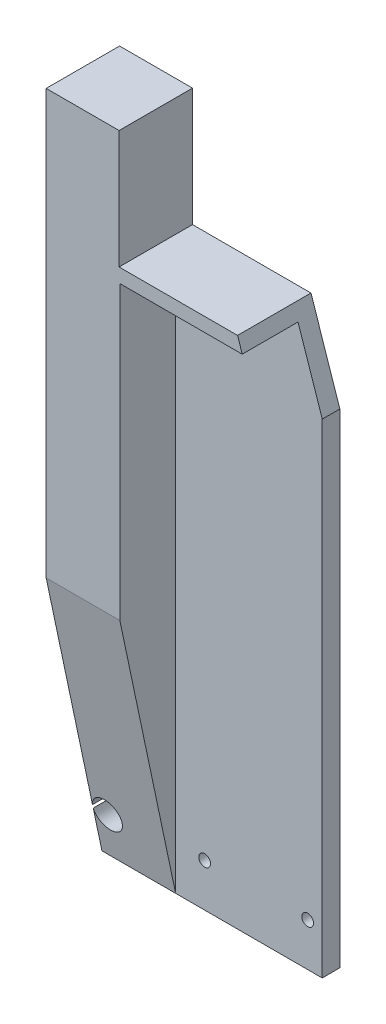
SolidWorks part; units mm, degrees
ref_plane "Front Plane" through (0, 0, 0) normal (0, 0, 1) x (1, 0, 0)
ref_plane "Top Plane" through (0, 0, 0) normal (0, 1, 0) x (1, 0, 0)
ref_plane "Right Plane" through (0, 0, 0) normal (1, 0, 0) x (0, 0, -1)
sketch "Sketch1" plane through (0, 0, 0) normal (0, 0, 1) x (1, 0, 0)
  line L0 (-37.5, -103.0682) -> (-37.5, -117.1625)
  line L1 (-37.5, -117.1625) -> (-12.416, -117.1625)
  line L2 (-12.416, -117.1625) -> (-12.416, -27.1625)
  line L3 (-37.5, -27.1625) -> (-37.5, -101.9314)
  line L4 (27.6676, 76.913) -> (-12.666, 76.913)
  line L5 (-12.666, 76.913) -> (-12.666, 117.1625)
  line L6 (-12.666, 117.1625) -> (-37.5, 117.1625)
  line L7 (-37.5, 117.1625) -> (-37.5, -27.1625)
  line L8 (-12.416, -27.1625) -> (-12.416, 72.163)
  line L9 (-12.416, 72.163) -> (29.2626, 72.163)
  line L10 (29.2626, 72.163) -> (27.6676, 76.913)
  line L11 (37.5, 47.6318) -> (29.2626, 72.163)
  line L12 (29.2626, 72.163) -> (-12.416, 72.163)
  line L13 (-12.416, 72.163) -> (-12.416, -117.1625)
  line L14 (-12.416, -117.1625) -> (37.5, -117.1625)
  line L15 (37.5, -117.1625) -> (37.5, 47.6318)
  line L16 (-12.416, -27.1625) -> (-37.5, -27.1625)
  line L17 (27.6676, 76.913) -> (-12.666, 76.913)
  line L18 (-12.666, 76.913) -> (-12.666, 117.1625)
  line L19 (-12.666, 117.1625) -> (-37.5, 117.1625)
  line L20 (-37.5, 117.1625) -> (-37.5, -27.1625)
  line L21 (-12.416, -27.1625) -> (-12.416, 72.163)
  line L22 (-12.416, 72.163) -> (29.2626, 72.163)
  line L23 (29.2626, 72.163) -> (27.6676, 76.913)
  line L24 (-37.5, -103.0682) -> (-37.5, -117.1625)
  line L25 (-37.5, -117.1625) -> (-12.416, -117.1625)
  line L26 (-12.416, -117.1625) -> (-12.416, -27.1625)
  line L27 (-37.5, -27.1625) -> (-37.5, -101.9314)
  arc A0 (-37.5, -103.0682) -> (-37.5, -101.9314) centre (-32.5324, -102.4998) ccw
  circle A1 centre (32.5324, -102.5039) radius 2
  circle A2 centre (-32.5324, -102.4998) radius 2
  circle A3 centre (-2.542, -102.5039) radius 2
  arc A4 (-37.5, -103.0682) -> (-37.5, -101.9314) centre (-32.5324, -102.4998) ccw
  circle A5 centre (32.5324, -102.5039) radius 1.4 construction
  circle A6 centre (-2.542, -102.5039) radius 1.4 construction
extrude "Boss-Extrude1" add sketch "Sketch1" along normal blind 6 contours L16 L8 L9 L10 L4 L5 L6 L7 | A0 L0 L1 L2 L16 L3 | L14 L15 L11 L9 L8 L2 A3 A1 region at (-24.6851, -71.0694, 0) region at (12.2947, -23.2213, 0) region at (-23.3072, 46.3693, 0)
extrude "Boss-Extrude2" add sketch "Sketch1<4>" along normal blind 25 contours L16 L8 L9 L10 L4 L5 L6 L7 | A0 L0 L1 L2 L16 L3 region at (-24.6851, -71.0694, 0) region at (-23.3072, 46.3693, 0)
sketch "Sketch1<4>" plane through (0, 0, 0) normal (0, 0, 1) x (1, 0, 0) same geometry as "Sketch1"
sketch "Sketch2" plane through (-12.416, 0, 0) normal (1, 0, 0) x (0, 0, -1)
  line L0 (-25, -27.1625) -> (-6, -117.1625)
  line L1 (-25, -117.1625) -> (-25, 72.163) construction
  line L2 (-6, -117.1625) -> (-25, -117.1625)
  line L3 (-25, -117.1625) -> (-25, -27.1625)
  dimension "D1" = 90
extrude "Cut-Extrude1" cut sketch "Sketch2" against normal blind 26
